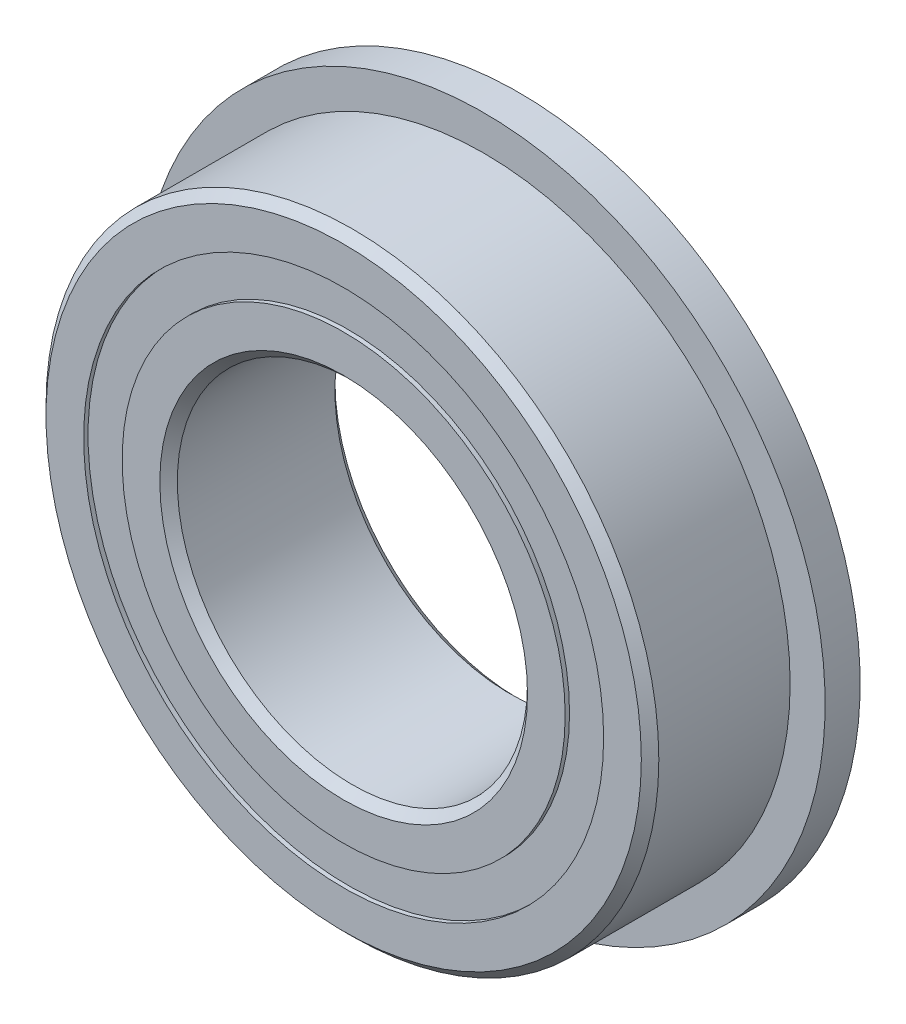
SolidWorks part; units mm, degrees
material "Alloy Steel"
ref_plane "Front Plane" through (0, 0, 0) normal (0, 0, 1) x (1, 0, 0)
ref_plane "Top Plane" through (0, 0, 0) normal (0, 1, 0) x (1, 0, 0)
ref_plane "Right Plane" through (0, 0, 0) normal (1, 0, 0) x (0, 0, -1)
sketch "Sketch1" plane through (0, 0, 0) normal (1, 0, 0) x (0, 0, -1)
  line L0 (-2, 0) -> (2, 0) construction
  line L1 (0, 7) -> (0, -7) construction
  line L2 (1.8, 7) -> (-1.8, 7)
  line L3 (-1.8, 7) -> (-2, 6.8)
  line L4 (-2, 6.8) -> (-2, 5.9396)
  line L5 (-2, 5.9396) -> (-0.8889, 5.9396)
  line L6 (2, 5.9396) -> (0.8889, 5.9396)
  line L7 (2, 6.8) -> (2, 5.9396)
  line L8 (1.8, 7) -> (2, 6.8)
  line L9 (0, 7) -> (0, 5.5) construction
  line L10 (0, 5.5) -> (0, 4) construction
  arc A0 (-0.8889, 5.9396) -> (0.8889, 5.9396) centre (0, 5.5) cw
  point P14 (0, 4)
  dimension "D3" = 1.7778
  dimension "D1" = 45
  dimension "Width" = 4
  dimension "OD" = 14
  dimension "D2" = 0.2
  dimension "Shaft Dia" = 8
  dimension "D4" = 0.4396
revolve "Revolve1" add sketch "Sketch1" angle 360 about L0
sketch "Sketch3" plane through (0, 0, 0) normal (1, 0, 0) x (0, 0, -1)
  line L0 (-2, 5.0604) -> (-0.8889, 5.0604)
  line L1 (0, 7) -> (0, -7) construction
  line L2 (-2, 6.8) -> (-2, 5.9396) construction
  line L3 (-2, 5.0604) -> (-2, 4.2)
  line L4 (-1.8, 7) -> (-2, 6.8) construction
  line L5 (-2, 4.2) -> (-1.8, 4)
  line L6 (-1.8, 4) -> (1.8, 4)
  line L7 (1.8, 7) -> (1.8, -7) construction
  line L8 (1.8, 4) -> (2, 4.2)
  line L9 (2, -6.8) -> (2, 6.8) construction
  line L10 (2, 4.2) -> (2, 5.0604)
  line L11 (2, 5.0604) -> (0.8889, 5.0604)
  line L13 (1.8, 7) -> (2, 6.8) construction
  arc A0 (0.8889, 5.9396) -> (-0.8889, 5.9396) centre (0, 5.5) ccw construction
  arc A1 (0.8889, 5.0604) -> (-0.8889, 5.0604) centre (0, 5.5) cw
revolve "Revolve3" add sketch "Sketch3" angle 360 about L0
sketch "Sketch4" plane through (0, 0, 0) normal (1, 0, 0) x (0, 0, -1)
  line L0 (-0.9916, 5.5) -> (0.9916, 5.5)
  arc A2 (-0.9916, 5.5) -> (0.9916, 5.5) centre (0, 5.5) cw
  arc A3 (0.8889, 5.9396) -> (-0.8889, 5.9396) centre (0, 5.5) ccw construction
revolve "Revolve4" add sketch "Sketch4" angle 360 about L0
ref_axis "Axis1" through (0, 0, -2) along (0, 0, 1)
pattern_circular "CirPattern1" count 12 every 30 about axis through (0, 0, -2) along (0, 0, 1) of bodies 104
sketch "Sketch5" plane through (0, 0, 0) normal (1, 0, 0) x (0, 0, -1)
  line L0 (-2, 5.9396) -> (-0.8889, 5.9396) construction
  line L1 (-1.9, 5.9396) -> (-0.9916, 5.9396)
  line L2 (-1.9, 5.9396) -> (-1.9, 5.0604)
  line L3 (-1.9, 5.0604) -> (-0.9916, 5.0604)
  line L4 (-0.9916, 5.9396) -> (-0.9916, 5.0604)
  line L5 (-2, 5.0604) -> (-0.8889, 5.0604) construction
  line L6 (2, 5.9396) -> (0.8889, 5.9396) construction
  line L7 (1.9, 5.9396) -> (0.9916, 5.9396)
  line L8 (1.9, 5.9396) -> (1.9, 5.0604)
  line L9 (1.9, 5.0604) -> (0.9916, 5.0604)
  line L10 (0.9916, 5.9396) -> (0.9916, 5.0604)
  line L11 (2, 5.0604) -> (0.8889, 5.0604) construction
  line L12 (-1.8, 7) -> (-2, 6.8) construction
  point P18 (-1.9, 6.9)
revolve "Revolve5" add sketch "Sketch5" angle 360 about L0
sketch "Sketch6" plane through (0, 0, 0) normal (1, 0, 0) x (0, 0, -1)
  line L0 (2, 0) -> (-2, 0) construction
  line L1 (2, 5.9396) -> (1.2, 5.9396)
  line L2 (2, 5.9396) -> (2, 7.8)
  line L3 (2, 7.8) -> (1.2, 7.8)
  line L4 (1.2, 5.9396) -> (1.2, 7.8)
  dimension "Th" = 0.8
  dimension "Flange OD" = 15.6
revolve "Revolve6" add sketch "Sketch6" angle 360 about L0
equation "\"D2@Sketch1\" = \"Width@Sketch1\"*.05"
equation "\"D3@Sketch1\" = \"Width@Sketch1\"/2.25"
equation "\"D4@Sketch1\" = (((\"OD@Sketch1\"-\"Width@Sketch1\")/2)/3.25)/3.5"
equation "\"D2@CirPattern1\" = 360/\"Balls@CirPattern1\""
